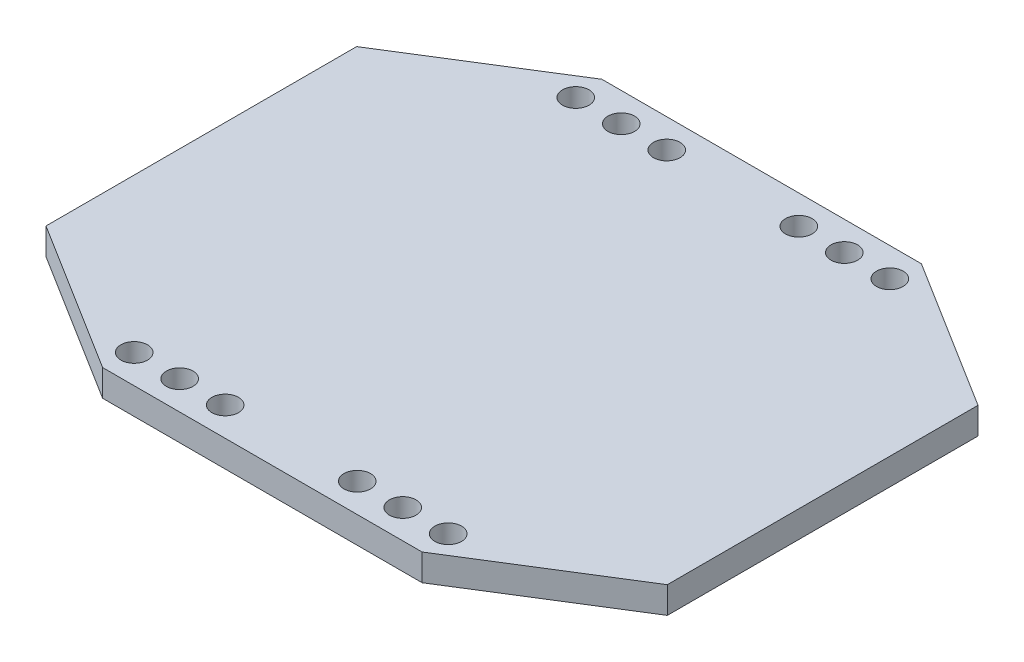
SolidWorks part; units mm, degrees
ref_plane "Front Plane" through (0, 0, 0) normal (0, 0, 1) x (1, 0, 0)
ref_plane "Top Plane" through (0, 0, 0) normal (0, 1, 0) x (1, 0, 0)
ref_plane "Right Plane" through (0, 0, 0) normal (1, 0, 0) x (0, 0, -1)
sketch "Sketch2" plane through (0, 0, 0) normal (0, 1, 0) x (1, 0, 0)
  line L0 (-28, -14) -> (-28, 14)
  line L1 (-28, 17.5) -> (28, 17.5) construction
  line L2 (-28, 17.5) -> (-28, -17.5) construction
  line L3 (-28, -17.5) -> (28, -17.5) construction
  line L4 (28, 17.5) -> (28, -17.5) construction
  line L5 (-28, 17.5) -> (28, -17.5) construction
  line L6 (-28, -17.5) -> (28, 17.5) construction
  line L7 (-28, 14) -> (-14.3972, 22.5)
  line L8 (28, 14) -> (14.3972, 22.5)
  line L9 (28, 14) -> (28, -14)
  line L10 (-14.3972, 22.5) -> (14.3972, 22.5)
  line L11 (-28, -14) -> (-14.3972, -22.5)
  line L12 (-14.3972, -22.5) -> (14.3972, -22.5)
  line L13 (14.3972, -22.5) -> (28, -14)
  circle A0 centre (-20, 9.5) radius 8 construction
  point P4 (0, 0)
  point P13 (0, 0)
  point P15 (0, 0)
  dimension "D3" = 16
  dimension "D1" = 56
  dimension "D2" = 35
  dimension "D4" = 8
  dimension "D5" = 8
  dimension "D6" = 3.5
  dimension "D7" = 3.5
  dimension "D8" = 58
  dimension "D9" = 5
  dimension "D10" = 58
extrude "Boss-Extrude1" add sketch "Sketch2" along normal mid plane 2.4
sketch "Sketch3" plane through (0, 1.2, 0) normal (0, 1, 0) x (1, 0, 0)
  line L0 (0, 0) -> (-26.4999, 42.3999) construction
  line L1 (0, 0) -> (-17.5, 0) construction
  line L2 (-17.5, 0) -> (-17.5, 28) construction
  line L3 (-33.2839, 38.1599) -> (-19.716, 46.6399) construction
  line L4 (-19.716, 46.6399) -> (-2.756, 19.504) construction
  line L5 (14.3972, 22.5) -> (-14.3972, 22.5) construction
  line L6 (-33.2839, 38.1599) -> (-16.324, 11.024) construction
  line L7 (-16.324, 11.024) -> (-2.756, 19.504) construction
  line L8 (-20.3715, 17.5) -> (-5.9623, 17.5) construction
  line L9 (-5.9623, 17.5) -> (-1.5035, 17.5) construction
  line L11 (-1.5035, 17.5) -> (-2.756, 19.504) construction
  line L12 (0, 0) -> (0, 22.5) construction
  line L13 (-14.1516, 19.9) -> (-5.9516, 19.9) construction
  circle A0 centre (-26.4999, 42.3999) radius 8 construction
  circle A1 centre (-14.1516, 19.9) radius 1.2
  circle A2 centre (-10.0516, 19.9) radius 1.2
  circle A3 centre (-5.9516, 19.9) radius 1.2
  point P13 (0, 0)
  point P16 (0, 0)
  point P20 (0, 0)
  point P26 (0, 0)
  point P27 (0, 0)
  point P28 (0, 0)
  point P29 (0, 0)
  point P31 (0, 0)
  dimension "D5" = 8
  dimension "D7" = 2.4
  dimension "D1" = 17.5
  dimension "D2" = 28
  dimension "D3" = 50
  dimension "D4" = 16
  dimension "D6" = 32
  dimension "D8" = 4.1
  dimension "D9" = 4.1
  dimension "D10" = 2.6
  dimension "D12" = 5
  dimension "D11" = 2.5
extrude "Cut-Extrude1" cut sketch "Sketch3" against normal through all
mirror "Mirror1" about plane through (0, 0, 0) normal (1, 0, 0) of "Cut-Extrude1"
mirror "Mirror2" about plane through (0, 0, 0) normal (0, 0, 1) of "Cut-Extrude1", "Mirror1"
equation "\"D7@Sketch2\"=\"D6@Sketch2\""
equation "\"D10@Sketch2\"=\"D8@Sketch2\""
equation "\"D9@Sketch3\"=\"D8@Sketch3\""
